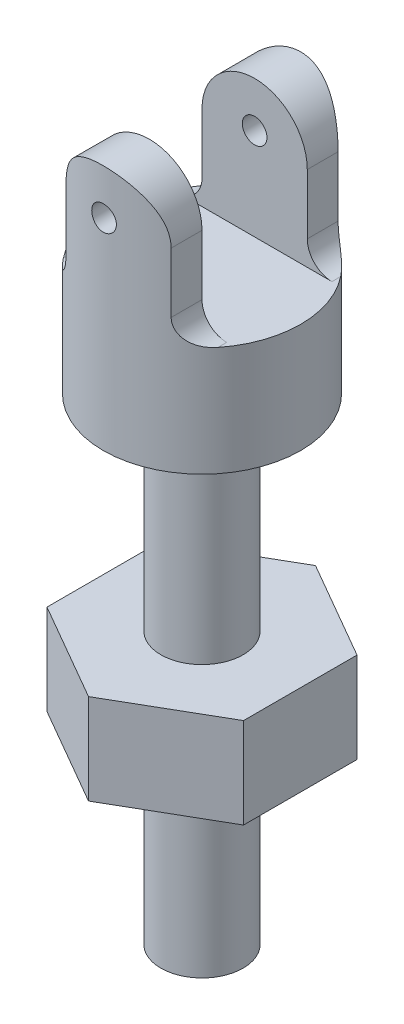
SolidWorks part; units mm, degrees
ref_plane "Front Plane" through (0, 0, 0) normal (0, 0, 1) x (1, 0, 0)
ref_plane "Top Plane" through (0, 0, 0) normal (0, 1, 0) x (1, 0, 0)
ref_plane "Right Plane" through (0, 0, 0) normal (1, 0, 0) x (0, 0, -1)
sketch "Sketch1" plane through (0, 0, 0) normal (0, 1, 0) x (1, 0, 0)
  circle A0 centre (0, 0) radius 6
  dimension "D1" = 12
extrude "Boss-Extrude1" add sketch "Sketch1" along normal blind 15
sketch "Sketch2" plane through (0, 0, 0) normal (1, 0, 0) x (0, 0, -1)
  line L0 (6, 15) -> (-6, 15) construction
  line L1 (-3.2, 15) -> (3.2, 15)
  line L2 (-3.2, 15) -> (-3.2, 6.65)
  line L3 (-3.2, 6.65) -> (3.2, 6.65)
  line L4 (3.2, 15) -> (3.2, 6.65)
  line L5 (-6, 0) -> (6, 0) construction
  point P8 (0, 6.65)
  dimension "D1" = 6.65
  dimension "D2" = 6.4
extrude "Cut-Extrude1" cut sketch "Sketch2" against normal through all both and the other way through all contours L2 L1 L4 L3
sketch "Sketch3" plane through (0, 0, 0) normal (0, 0, 1) x (1, 0, 0)
  line L0 (5.0754, 15) -> (-5.0754, 15) construction
  line L1 (-3.2, 11.8) -> (-3.2, 8.15)
  line L2 (-4.7, 6.65) -> (-5.0754, 6.65)
  line L3 (-5.0754, 15) -> (-5.0754, 6.65) construction
  line L4 (5.0754, 15) -> (-5.0754, 15)
  line L5 (-5.0754, 15) -> (-5.0754, 6.65)
  line L7 (0, -6.6) -> (0, 6.6) construction
  line L8 (5.0754, 15) -> (5.0754, 6.65)
  line L9 (4.7, 6.65) -> (5.0754, 6.65)
  line L10 (3.2, 11.8) -> (3.2, 8.15)
  arc A0 (3.2, 11.8) -> (-3.2, 11.8) centre (0, 11.8) ccw
  arc A1 (-3.2, 8.15) -> (-4.7, 6.65) centre (-4.7, 8.15) cw
  arc A2 (3.2, 8.15) -> (4.7, 6.65) centre (4.7, 8.15) ccw
  circle A4 centre (0, 12.25) radius 0.75
  point P7 (0, 0)
  point P8 (0, 15)
  point P20 (0, 0)
  dimension "D1" = 6.4
  dimension "D2" = 1.5
  dimension "D3" = 1.5
  dimension "D4" = 2.75
extrude "Cut-Extrude2" cut sketch "Sketch3" against normal through all both and the other way through all contours A1 L1 A0 L4 L5 L2 | L10 A2 L9 L8 L4 A0 | A4 region at (3.9455, 11.3694, 0) region at (-3.9455, 11.3694, 0) region at (0, 12.25, 0)
sketch "Sketch4" plane through (0, 0, 0) normal (0, -1, 0) x (1, 0, 0)
  circle A0 centre (0, 0) radius 2.5
  dimension "D1" = 5
extrude "Boss-Extrude2" add sketch "Sketch4" along normal blind 29
ref_plane "Plane1" through (0, -18, 0) normal (0, -1, 0) x (-1, 0, 0)
sketch "Sketch5" plane through (0, -18, 0) normal (0, -1, 0) x (-1, 0, 0)
  line L1 (0, -6.8993) -> (5.975, -3.4497)
  line L2 (5.975, -3.4497) -> (5.975, 3.4497)
  line L3 (5.975, 3.4497) -> (0, 6.8993)
  line L4 (0, 6.8993) -> (-5.975, 3.4497)
  line L5 (-5.975, 3.4497) -> (-5.975, -3.4497)
  line L6 (-5.975, -3.4497) -> (0, -6.8993)
  circle A0 centre (0, 0) radius 5.975 construction
  point P1 (0, 0)
  point P10 (0, 0)
  dimension "D1" = 11.95
extrude "Boss-Extrude3" add sketch "Sketch5" against normal blind 5.5 contours L3 L4 L5 L6 L1 L2
